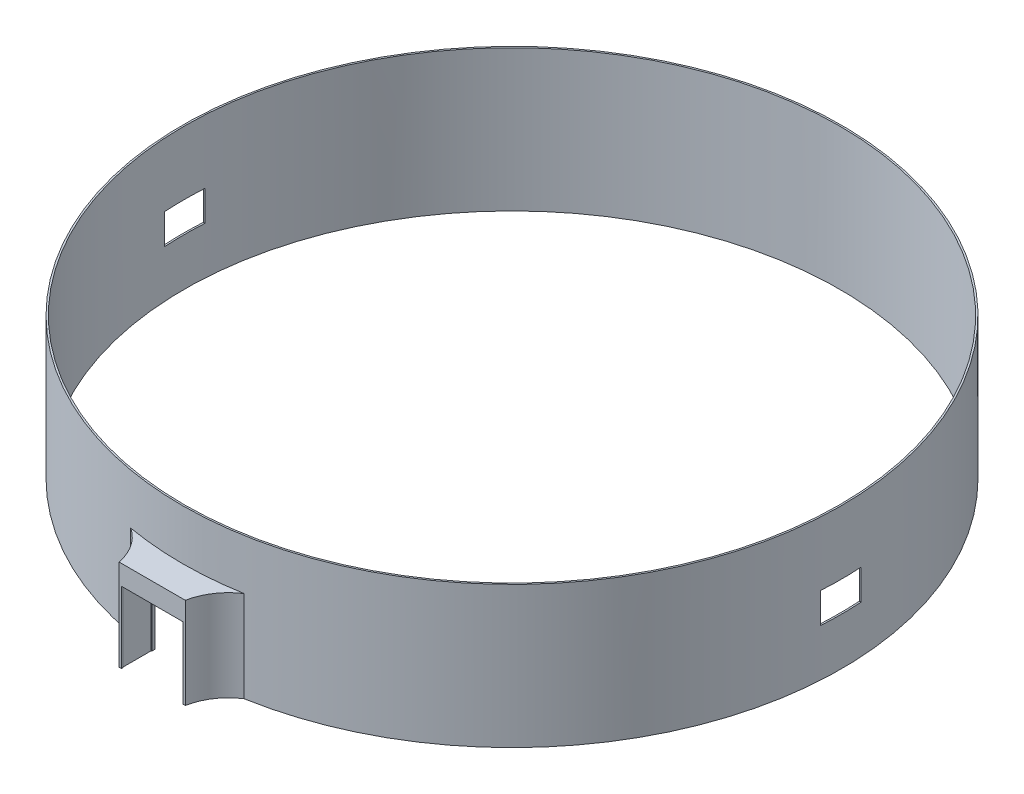
SolidWorks part; units mm, degrees
ref_plane "Front Plane" through (0, 0, 0) normal (0, 0, 1) x (1, 0, 0)
ref_plane "Top Plane" through (0, 0, 0) normal (0, 1, 0) x (1, 0, 0)
ref_plane "Right Plane" through (0, 0, 0) normal (1, 0, 0) x (0, 0, -1)
sketch "Sketch1" plane through (0, 0, 0) normal (0, 1, 0) x (1, 0, 0)
  circle A0 centre (0, 0) radius 9945.7494
  circle A1 centre (0, 0) radius 9850
extrude "Boss-Extrude1" add sketch "Sketch1" along normal blind 4267.2 contours A0
sketch "Sketch2" plane through (0, 4267.2, 0) normal (0, 1, 0) x (1, 0, 0)
  circle A0 centre (0, 0) radius 9895.7494
  circle A1 centre (0, 0) radius 9945.7494 construction
  dimension "D1" = 50
extrude "Cut-Extrude1" cut sketch "Sketch2" against normal blind 4267.2 contours A0
ref_plane "Plane2" through (0, 0, 9945.7494) normal (0, 0, 1) x (1, 0, 0)
sketch "Sketch4" plane through (0, 0, 9945.7494) normal (0, 0, 1) x (1, 0, 0)
  line L0 (0, -2346.96) -> (0, 2346.96) construction
  line L1 (1000, 0) -> (-1000, 0)
  line L2 (1000, 0) -> (1000, 2750)
  line L3 (1000, 2750) -> (-1000, 2750)
  line L4 (-1000, 0) -> (-1000, 2750)
  line L5 (1000, 0) -> (-1000, 2750) construction
  line L6 (1000, 2750) -> (-1000, 0) construction
  line L7 (10940.3244, 0) -> (-10940.3244, 0) construction
  point P0 (0, 1375)
  dimension "D1" = 2750
  dimension "D2" = 2000
extrude "Boss-Extrude2" add sketch "Sketch4" along normal blind 914.4 separate body
sketch "Sketch5" plane through (0, 0, 10860.1494) normal (0, 0, 1) x (1, 0, 0)
  line L0 (0, -2346.96) -> (0, 2346.96) construction
  line L1 (926.615, 0) -> (-926.615, 0)
  line L2 (926.615, 0) -> (926.615, 2153.23)
  line L3 (926.615, 2153.23) -> (-926.615, 2153.23)
  line L4 (-926.615, 0) -> (-926.615, 2153.23)
  line L5 (926.615, 0) -> (-926.615, 2153.23) construction
  line L6 (926.615, 2153.23) -> (-926.615, 0) construction
  line L7 (-1000, 0) -> (1000, 0) construction
  point P0 (0, 1076.615)
  dimension "D1" = 1853.23
  dimension "D2" = 2153.23
extrude "Cut-Extrude2" cut sketch "Sketch5" against normal mid plane 5000
sketch "Sketch6" plane through (-926.615, 0, 0) normal (1, 0, 0) x (0, 0, -1)
  line L0 (-10860.1494, 2153.23) -> (-10860.1494, 0) construction
  line L1 (-9945.7494, -75.4869) -> (-10810.1494, -75.4869)
  line L2 (-9945.7494, -75.4869) -> (-9945.7494, 2147.3115)
  line L3 (-9945.7494, 2147.3115) -> (-10810.1494, 2147.3115)
  line L4 (-10810.1494, -75.4869) -> (-10810.1494, 2147.3115)
  line L5 (-9945.7494, -75.4869) -> (-10810.1494, 2147.3115) construction
  line L6 (-9945.7494, 2147.3115) -> (-10810.1494, -75.4869) construction
  line L7 (-9945.7494, 2346.96) -> (-9945.7494, -2346.96) construction
  point P0 (-10377.9494, 1035.9123)
  point P7 (-9945.7494, 2147.3115)
  dimension "D1" = 50
extrude "Cut-Extrude3" cut sketch "Sketch6" against normal blind 16.77
mirror "Mirror1" about plane through (0, 0, 0) normal (1, 0, 0) of "Cut-Extrude3"
sketch "Sketch7" plane through (0, 2153.23, 0) normal (0, -1, 0) x (1, 0, 0)
  line L0 (0, -2346.96) -> (0, 2346.96) construction
  line L1 (935, 10041.6167) -> (-935, 10041.6167)
  line L2 (935, 10041.6167) -> (935, 10810.1494)
  line L3 (935, 10810.1494) -> (-935, 10810.1494)
  line L4 (-935, 10041.6167) -> (-935, 10810.1494)
  line L5 (935, 10041.6167) -> (-935, 10810.1494) construction
  line L6 (935, 10810.1494) -> (-935, 10041.6167) construction
  line L7 (-943.385, 10810.1494) -> (-926.615, 10810.1494) construction
  line L8 (926.615, 10860.1494) -> (-926.615, 10860.1494) construction
  point P0 (0, 10425.8831)
  dimension "D1" = 50
extrude "Cut-Extrude4" cut sketch "Sketch7" against normal blind 16.77
sketch "Sketch8" plane through (0, 0, 0) normal (0, 1, 0) x (1, 0, 0)
  line L1 (-2346.96, -9945.7494) -> (2346.96, -9945.7494) construction
  line L2 (-1000, -10860.1494) -> (-1000, -9945.7494) construction
  line L3 (-1000, -9945.7494) -> (-1000, -10860.1494)
  line L4 (0, -2346.96) -> (0, 2346.96) construction
  line L5 (1000, -9945.7494) -> (1000, -10860.1494)
  line L6 (-1000, -9895.349) -> (1000, -9895.349)
  line L7 (1000, -9945.7494) -> (-1000, -9945.7494)
  circle A0 centre (0, 0) radius 9945.7494 construction
  arc A1 (-1000, -10860.1494) -> (-1709.7578, -9797.6865) centre (-2617.2235, -11172.2028) ccw
  arc A2 (-1709.7578, -9797.6865) -> (-1000, -9895.349) centre (0, 0) ccw
  arc A3 (1000, -10860.1494) -> (1709.7578, -9797.6865) centre (2617.2235, -11172.2028) cw
  arc A4 (1709.7578, -9797.6865) -> (1000, -9895.349) centre (0, 0) cw
extrude "Boss-Extrude3" add sketch "Sketch8" along normal up to surface (2750 mm away) up to face at (0, 2750, 10402.9494)
sketch "Sketch9" plane through (0, 0, 9945.7494) normal (0, 0, 1) x (1, 0, 0)
  line L1 (926.615, -141.7417) -> (-926.615, -141.7417)
  line L2 (926.615, -141.7417) -> (926.615, 2153.23)
  line L3 (926.615, 2153.23) -> (-926.615, 2153.23)
  line L4 (-926.615, -141.7417) -> (-926.615, 2153.23)
  line L5 (926.615, -141.7417) -> (-926.615, 2153.23) construction
  line L6 (926.615, 2153.23) -> (-926.615, -141.7417) construction
  point P0 (0, 1005.7441)
extrude "Cut-Extrude5" cut sketch "Sketch9" against normal blind 4000
sketch "Sketch10" plane through (0, 0, 0) normal (1, 0, 0) x (0, 0, -1)
  line L0 (0, 2424.9179) -> (0, -2424.9179) construction
  line L1 (609.6, 1430.1679) -> (-609.6, 1430.1679)
  line L2 (609.6, 1430.1679) -> (609.6, 2344.5679)
  line L3 (609.6, 2344.5679) -> (-609.6, 2344.5679)
  line L4 (-609.6, 1430.1679) -> (-609.6, 2344.5679)
  line L5 (609.6, 1430.1679) -> (-609.6, 2344.5679) construction
  line L6 (609.6, 2344.5679) -> (-609.6, 1430.1679) construction
  point P0 (0, 1887.3679)
  dimension "D1" = 914.4
  dimension "D2" = 90
  dimension "D3" = 1219.2
extrude "Cut-Extrude6" cut sketch "Sketch10" against normal through all both and the other way through all
